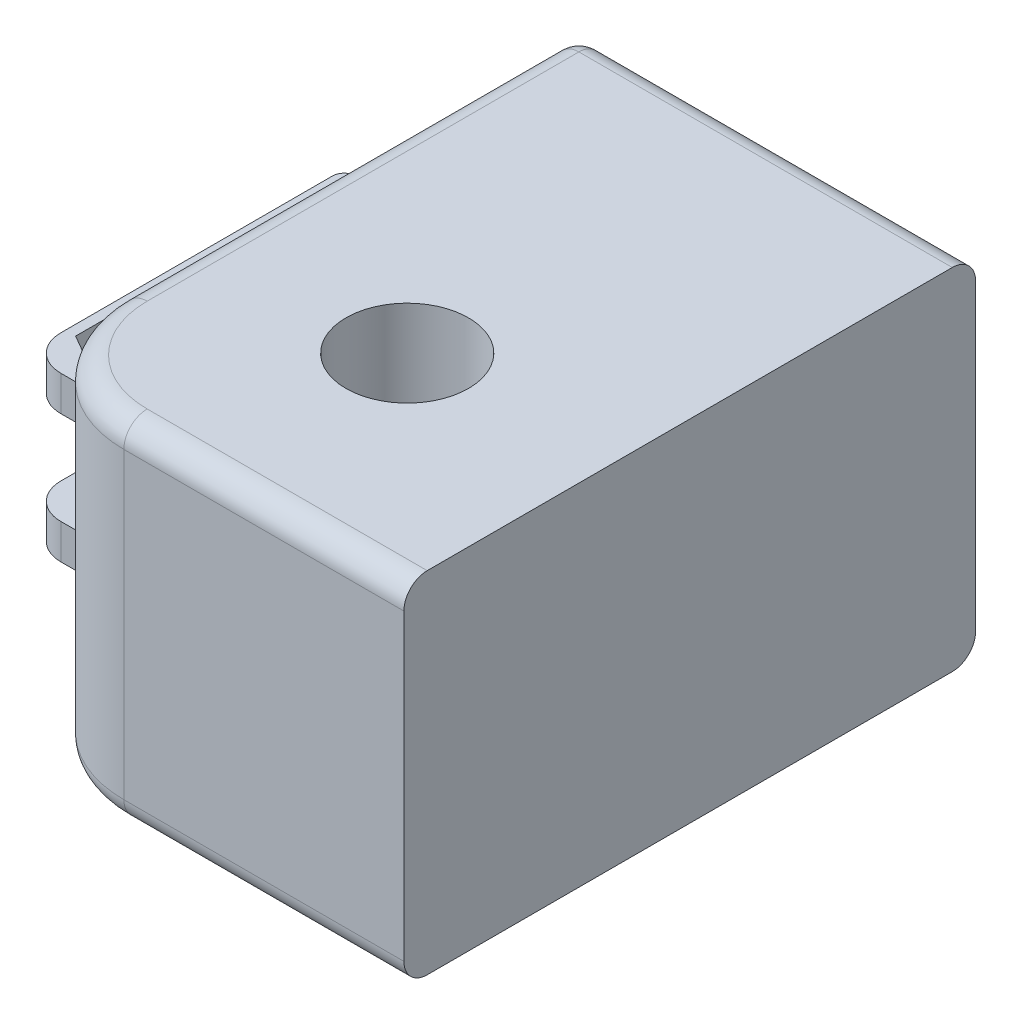
SolidWorks part; units mm, degrees
ref_plane "Front Plane" through (0, 0, 0) normal (0, 0, 1) x (1, 0, 0)
ref_plane "Top Plane" through (0, 0, 0) normal (0, 1, 0) x (1, 0, 0)
ref_plane "Right Plane" through (0, 0, 0) normal (1, 0, 0) x (0, 0, -1)
sketch "Sketch1" plane through (0, 0, 0) normal (0, 0, 1) x (1, 0, 0)
  line L1 (17, -15) -> (-17, -15)
  line L2 (17, -15) -> (17, 15)
  line L3 (17, 15) -> (-17, 15)
  line L4 (-17, -15) -> (-17, 15)
  dimension "D1" = 34
  dimension "D2" = 30
  dimension "D3" = 15
  dimension "D4" = 17
extrude "Boss-Extrude1" add sketch "Sketch1" along normal blind 49
sketch "Sketch2" plane through (0, 0, 0) normal (0, 0, -1) x (-1, 0, 0)
  line L0 (-17, -15) -> (-17, 15) construction
  line L1 (17, -15) -> (-17, -15) construction
  circle A4 centre (-12, 9) radius 2 construction
  circle A5 centre (-12, -9) radius 2 construction
  circle A6 centre (12, -9) radius 2 construction
  circle A7 centre (12, 9) radius 2 construction
  circle A8 centre (12, -9) radius 2.1
  circle A9 centre (12, 9) radius 2.1
  circle A10 centre (-12, -9) radius 2.1
  circle A11 centre (-12, 9) radius 2.1
  dimension "D1" = 4
  dimension "D2" = 5
  dimension "D3" = 29
  dimension "D4" = 6
  dimension "D5" = 24
  dimension "D6" = 0.1
extrude "Cut-Extrude1" cut sketch "Sketch2" against normal blind 6
sketch "Sketch5" plane through (0, -15, 0) normal (0, -1, 0) x (1, 0, 0)
  line L0 (17, 49) -> (17, 0) construction
  line L2 (-17, 49) -> (17, 49) construction
  circle A1 centre (0, 31.7136) radius 11 construction
  circle A3 centre (0, 31.7136) radius 11.15
  dimension "D1" = 22
  dimension "D2" = 17
  dimension "D3" = 17.2864
  dimension "D4" = 0.15
extrude "Cut-Extrude2" cut sketch "Sketch5" against normal blind 12.5
sketch "Sketch6" plane through (0, 15, 0) normal (0, 1, 0) x (1, 0, 0)
  circle A1 centre (0, -31.7136) radius 5.1 construction
  circle A2 centre (0, -31.7136) radius 5.25
  point P1 (0, 0)
  dimension "D1" = 10.2
  dimension "D4" = 0.15
extrude "Cut-Extrude3" cut sketch "Sketch6" against normal blind 17.5
sketch "Sketch7" plane through (0, -2.5, 0) normal (0, -1, 0) x (1, 0, 0)
  circle A4 centre (7.9785, 31.127) radius 1.75 construction
  circle A5 centre (-0.5866, 39.6921) radius 1.75 construction
  circle A6 centre (-7.9785, 31.127) radius 1.75 construction
  circle A7 centre (0.5866, 23.7351) radius 1.75 construction
  circle A8 centre (-7.9785, 31.127) radius 2.1
  circle A9 centre (-0.5866, 39.6921) radius 2.1
  circle A10 centre (7.9785, 31.127) radius 2.1
  circle A11 centre (0.5866, 23.7351) radius 2.1
  circle A12 centre (0, 31.7136) radius 5.25 construction
  dimension "D2" = 4.2
  dimension "D3" = 0.5866
  dimension "D4" = 7.9785
  dimension "D5" = 0.5866
  dimension "D6" = 7.9785
  dimension "D7" = 0.5866
  dimension "D8" = 7.9785
  dimension "D9" = 0.5866
  dimension "D10" = 7.9785
  dimension "D1" = 0.35
extrude "Cut-Extrude4" cut sketch "Sketch7" against normal blind 6
chamfer "Chamfer1" distance 1 angle 45 4 edges at (7.9785, -2.5, 29.027) (-0.5866, -2.5, 37.5921) (-7.9785, -2.5, 29.027) (0.5866, -2.5, 21.6351)
chamfer "Chamfer2" distance 1 angle 45 4 edges at (9.9, -9, 0) (-14.1, -9, 0) (-14.1, 9, 0) (9.9, 9, 0)
fillet "Fillet1" radius 10 1 edges at (-17, 0, 49)
fillet "Fillet2" radius 2 9 edges at (-17, 15, 19.5) (5, 15, 49) (5, -15, 49) (-17, -15, 19.5) (0, -15, 0) (-17, 0, 0) (0, 15, 0) (-14.0711, 15, 46.0711) (-14.0711, -15, 46.0711)
sketch "Sketch8" plane through (17, 0, 0) normal (1, 0, 0) x (0, 0, -1)
  line L1 (-42, 9) -> (-7, 9) construction
  line L2 (-42, 9) -> (-42, -9) construction
  line L3 (-42, -9) -> (-7, -9) construction
  line L4 (-7, 9) -> (-7, -9) construction
  line L5 (-42, 9) -> (-7, -9) construction
  line L6 (-42, -9) -> (-7, 9) construction
  line L7 (-47, 15) -> (-2, 15) construction
  circle A0 centre (-42, 9) radius 2.075
  circle A1 centre (-7, 9) radius 2.075
  circle A2 centre (-7, -9) radius 2.075
  circle A3 centre (-42, -9) radius 2.075
  point P0 (-24.5, 0)
  point P14 (-24.5, 15)
  dimension "D1" = 4.15
  dimension "D2" = 35
  dimension "D3" = 18
extrude "Cut-Extrude5" [suppressed] cut sketch "Sketch8" against normal blind 6.5
chamfer "Chamfer3" [suppressed] distance 1.5 angle 45
sketch "Sketch9" plane through (0, 0, 0) normal (0, 1, 0) x (1, 0, 0)
  line L0 (-17, -40.0491) -> (-24.3539, -40.0491)
  line L1 (-17, -2) -> (-17, -39) construction
  line L2 (-24.3539, -40.0491) -> (-24.3539, -12.7622)
  line L3 (-24.3539, -12.7622) -> (-17, -12.7622)
  line L4 (-17, -12.7622) -> (-17, -40.0491)
  line L5 (-20.6, -35) -> (-20.6, -19)
  circle A1 centre (-20.6, -35) radius 1.625
  circle A2 centre (-20.6, -19) radius 1.625
  dimension "D3" = 3.25
  dimension "D1" = 3.6
  dimension "D2" = 16
extrude "Boss-Extrude2" add sketch "Sketch9" along normal blind 3 from offset 4 contours L4 L3 L2 L0 A2 A1 region at (-20.6839, 0, 26.3521)
mirror "Mirror1" about plane through (0, 0, 0) normal (0, 1, 0) of "Boss-Extrude2"
fillet "Fillet3" radius 3 2 edges at (-24.3539, 5.5, 40.0491) (-24.3539, -5.5, 40.0491)
fillet "Fillet4" radius 1 4 edges at (-24.3539, 5.5, 12.7622) (-17, 5.5, 12.7622) (-17, -5.5, 12.7622) (-24.3539, -5.5, 12.7622)
sketch "Sketch10" plane through (0, 7, 0) normal (0, 1, 0) x (1, 0, 0)
  line L1 (-17.725, -20.6599) -> (-17.725, -17.3401)
  line L2 (-17.725, -17.3401) -> (-20.6, -15.6802)
  line L3 (-20.6, -15.6802) -> (-23.475, -17.3401)
  line L4 (-23.475, -17.3401) -> (-23.475, -20.6599)
  line L5 (-23.475, -20.6599) -> (-20.6, -22.3198)
  line L6 (-20.6, -22.3198) -> (-17.725, -20.6599)
  line L7 (-17.725, -36.6599) -> (-17.725, -33.3401)
  line L8 (-17.725, -33.3401) -> (-20.6, -31.6802)
  line L9 (-20.6, -31.6802) -> (-23.475, -33.3401)
  line L10 (-23.475, -33.3401) -> (-23.475, -36.6599)
  line L11 (-23.475, -36.6599) -> (-20.6, -38.3198)
  line L12 (-20.6, -38.3198) -> (-17.725, -36.6599)
  circle A0 centre (-20.6, -19) radius 2.875 construction
  circle A1 centre (-20.6, -35) radius 2.875 construction
  dimension "D1" = 5.75
extrude "Cut-Extrude6" cut sketch "Sketch10" against normal blind 2
ref_plane "Plane1" through (0, 0, 18.18) normal (0, 0, -1) x (-1, 0, 0)
sketch "Sketch13" plane through (0, -15, 0) normal (0, -1, 0) x (1, 0, 0)
  line L0 (-14.3, 18.18) -> (14.3, 18.18) construction
  line L1 (-9, 25.73) -> (11, 25.73) construction
  line L2 (-9, 25.73) -> (-9, 10.63) construction
  line L3 (-9, 10.63) -> (11, 10.63) construction
  line L4 (11, 25.73) -> (11, 10.63) construction
  line L5 (-15, 2) -> (17, 2) construction
  circle A0 centre (-9, 25.73) radius 2.05
  circle A1 centre (11, 25.73) radius 2.05
  circle A2 centre (-9, 10.63) radius 2.05
  circle A3 centre (11, 10.63) radius 2.05
  point P10 (11, 18.18)
  point P15 (1, 2)
  point P16 (1, 10.63)
  dimension "D1" = 4.1
  dimension "D2" = 5.5
  dimension "D3" = 20
extrude "Cut-Extrude7" [suppressed] cut sketch "Sketch13" against normal through all
chamfer "Chamfer4" [suppressed] distance 1 angle 45
